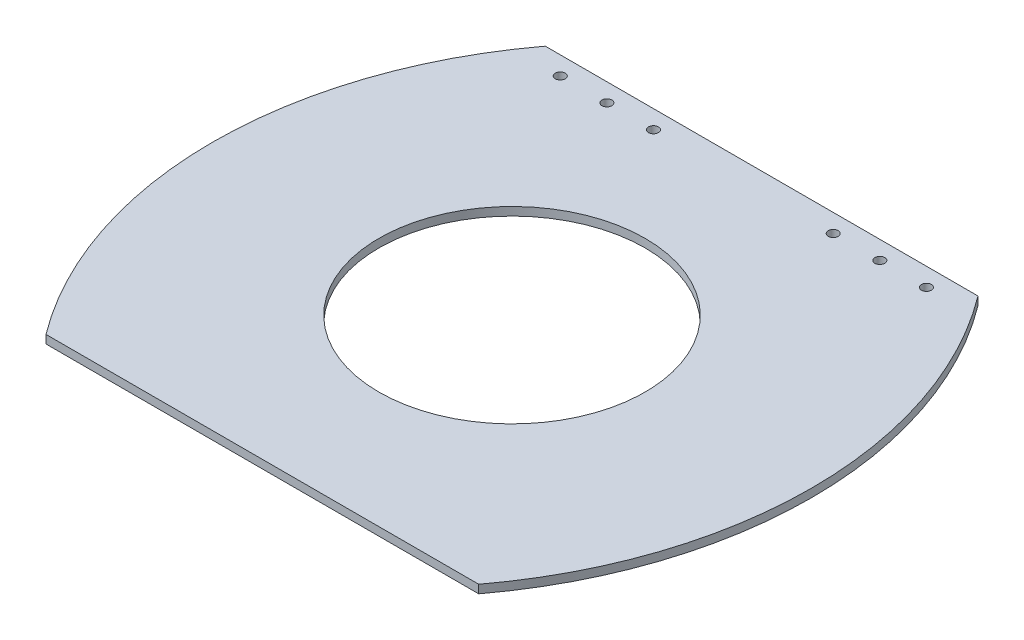
SolidWorks part; units mm, degrees
material "Silicon Rubber"
ref_plane "Front Plane" through (0, 0, 0) normal (0, 0, 1) x (1, 0, 0)
ref_plane "Top Plane" through (0, 0, 0) normal (0, 1, 0) x (1, 0, 0)
ref_plane "Right Plane" through (0, 0, 0) normal (1, 0, 0) x (0, 0, -1)
sketch "Lid case" plane through (0, 0, 0) normal (0, 1, 0) x (1, 0, 0)
  line L0 (-130, 150) -> (130, 150)
  line L1 (-130, -150) -> (130, -150)
  arc A0 (130, 150) -> (130, -150) centre (-70, 0) cw
  arc A1 (-130, 150) -> (-130, -150) centre (70, 0) ccw
  dimension "D6" = 250
  dimension "D7" = 250
  dimension "D1" = 260
  dimension "D2" = 130
  dimension "D3" = 150
  dimension "D4" = 150
  dimension "D5" = 130
extrude "Boss-Extrude1" add sketch "Lid case" along normal blind 5
ref_axis "Axis1" through (0, -54.3732, 0) along (0, 1, 0)
ref_plane "Plane1" through (0, 0, 0) normal (0, 0, 1) x (1, 0, 0)
sketch "Sketch2" plane through (0, 0, 0) normal (0, -1, 0) x (1, 0, 0)
  circle A0 centre (0, 0) radius 80
  dimension "D1" = 160
extrude "Cut-Extrude5" cut sketch "Sketch2" against normal blind 10
sketch "Sketch3" plane through (0, 5, 0) normal (0, 1, 0) x (1, 0, 0)
  circle A0 centre (-110, 139) radius 3
  circle A1 centre (-82, 139) radius 3
  circle A2 centre (-54, 139) radius 3
  circle A3 centre (54, 139) radius 3
  circle A4 centre (82, 139) radius 3
  circle A5 centre (110, 139) radius 3
  dimension "D7" = 6
  dimension "D1" = 28
  dimension "D2" = 28
  dimension "D3" = 28
  dimension "D4" = 28
  dimension "D5" = 11
  dimension "D6" = 20
  dimension "D8" = 20
extrude "Cut-Extrude6" cut sketch "Sketch3" against normal through all
